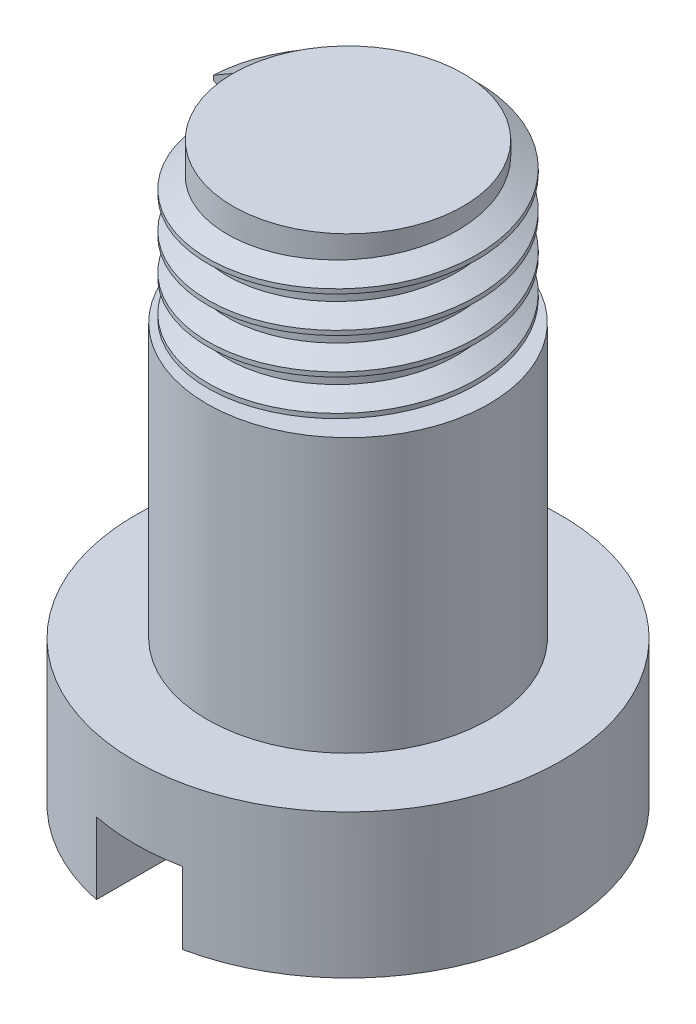
SolidWorks part; units mm, degrees
ref_plane "Front Plane" through (0, 0, 0) normal (0, 0, 1) x (1, 0, 0)
ref_plane "Top Plane" through (0, 0, 0) normal (0, 1, 0) x (1, 0, 0)
ref_plane "Right Plane" through (0, 0, 0) normal (1, 0, 0) x (0, 0, -1)
sketch "Sketch1" plane through (0, 0, 0) normal (0, 1, 0) x (1, 0, 0)
  circle A0 centre (0, 0) radius 7.4
  dimension "D1" = 14.8
extrude "Boss-Extrude1" add sketch "Sketch1" along normal blind 5
sketch "Sketch2" plane through (0, 5, 0) normal (0, 1, 0) x (1, 0, 0)
  circle A0 centre (0, 0) radius 4.9
  dimension "D1" = 9.8
extrude "Boss-Extrude2" add sketch "Sketch2" along normal blind 15
sketch "Sketch5" plane through (0, 0, 0) normal (0, -1, 0) x (1, 0, 0)
  line L1 (-1.5, -7.4) -> (1.5, -7.4)
  line L2 (-1.5, -7.4) -> (-1.5, 7.4)
  line L3 (-1.5, 7.4) -> (1.5, 7.4)
  line L4 (1.5, -7.4) -> (1.5, 7.4)
  circle A0 centre (0, 0) radius 7.4 construction
  point P4 (0, 7.4)
  point P9 (0, -7.4)
  dimension "D1" = 14.8
  dimension "D2" = 3
sketch "Sketch13" plane through (0, 20, 0) normal (0, 1, 0) x (1, 0, 0)
  circle A0 centre (0, 0) radius 4
  dimension "D1" = 8
extrude "Cut-Extrude4" cut sketch "Sketch13" against normal blind 5.5 flip side to cut
thread "Thread2" pitch 1.25 method extrude trim with end face yes profile "Thread Profile4" start angle 0, offset 0, length 0, pitch 1.25, diameter 8
ref_plane "Plane4" through (-4, 20, 0) normal (0, 0, 1) x (-1, 0, 0)
sketch "Thread Profile4" plane through (-4, 20, 0) normal (0, 0, 1) x (-1, 0, 0)
  line L0 (0, 0) -> (0, 1.25) construction
  line L1 (0, 0) -> (0.6766, 0.3906)
  line L2 (0.6766, 0.3906) -> (0.6766, 0.5469)
  line L3 (0.6766, 0.5469) -> (0, 0.9375)
  line L4 (0.6766, 0.4687) -> (0, 0.4687) construction
  line L11 (0, 0) -> (0, 0.9375)
  point P2 (0, 0)
  dimension "Pitch" = 1.25
  dimension "Profile_Angle" = 60
  dimension "Profile_Land" = 0.1562
  dimension "Profile_Height" = 0.6766
extrude "Cut-Extrude5" cut sketch "Sketch5" against normal blind 2.5
